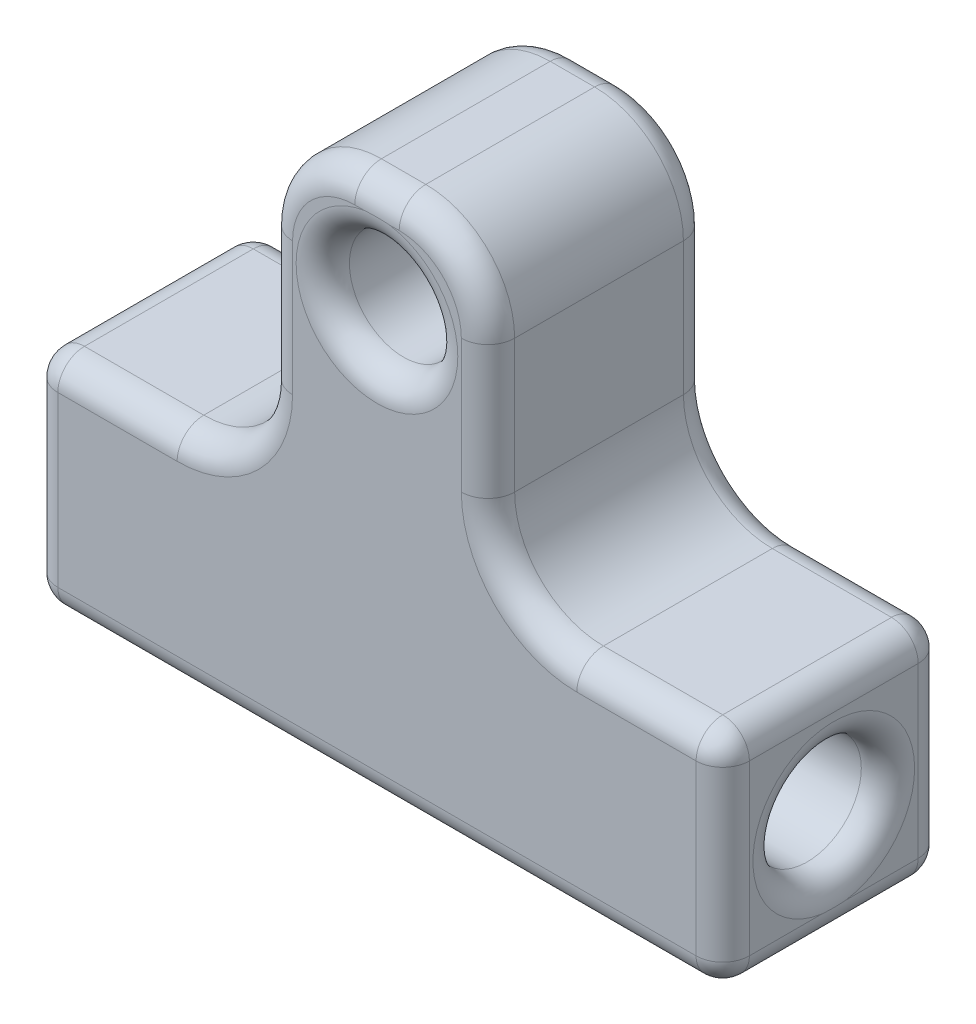
SolidWorks part; units mm, degrees
ref_plane "Front Plane" through (0, 0, 0) normal (0, 0, 1) x (1, 0, 0)
ref_plane "Top Plane" through (0, 0, 0) normal (0, 1, 0) x (1, 0, 0)
ref_plane "Right Plane" through (0, 0, 0) normal (1, 0, 0) x (0, 0, -1)
sketch "Sketch1" plane through (0, 0, 0) normal (0, 0, 1) x (1, 0, 0)
  line L0 (0, 42.6446) -> (0, -51.4876) construction
  line L1 (-40.9091, 0) -> (51.7355, 0) construction
  line L2 (22.5, -5) -> (38.9256, -5)
  line L3 (-2.5, 30) -> (2.5, 30)
  line L4 (-12.5, 20) -> (-12.5, 5)
  line L5 (-12.5, -30) -> (12.5, -30)
  line L6 (12.5, 20) -> (12.5, 5)
  line L7 (-12.5, 30) -> (12.5, -30) construction
  line L8 (-12.5, -30) -> (12.5, 30) construction
  line L9 (-38.9256, -5) -> (-22.5, -5)
  line L10 (-38.9256, -5) -> (-38.9256, -30)
  line L11 (-38.9256, -30) -> (38.9256, -30)
  line L12 (38.9256, -5) -> (38.9256, -30)
  line L13 (-38.9256, -5) -> (38.9256, -30) construction
  line L14 (-38.9256, -30) -> (38.9256, -5) construction
  arc A0 (2.5, 30) -> (12.5, 20) centre (2.5, 20) cw
  arc A1 (-2.5, 30) -> (-12.5, 20) centre (-2.5, 20) ccw
  arc A2 (12.5, 5) -> (22.5, -5) centre (22.5, 5) ccw
  arc A3 (-12.5, 5) -> (-22.5, -5) centre (-22.5, 5) cw
  circle A4 centre (0, 18) radius 6.1
  point P5 (0, 0)
  point P10 (0, -17.5)
  point P25 (12.5, -5)
  dimension "D4" = 10
  dimension "D5" = 12.2
  dimension "D1" = 25
  dimension "D2" = 60
  dimension "D3" = 25
  dimension "D6" = 12
extrude "Boss-Extrude1" add sketch "Sketch1" along normal blind 25 contours A3 L9 L10 L11 L12 L2 A2 L6 A0 L3 A1 L4 | A4
sketch "Sketch2" plane through (38.9256, 0, 0) normal (1, 0, 0) x (0, 0, -1)
  line L0 (-12.5, -5) -> (-12.5, -30) construction
  line L1 (-25, -5) -> (0, -5) construction
  line L2 (-25, -30) -> (0, -30) construction
  circle A0 centre (-12.5, -18) radius 6.1
  dimension "D1" = 12.2
  dimension "D2" = 12
extrude "Cut-Extrude1" cut sketch "Sketch2" against normal through all
fillet "Fillet1" radius 3 32 edges at (-38.9256, -5, 12.5) (-38.9256, -30, 12.5) (-38.9256, -18, 6.4) (6.1, 18, 0) (-15.4289, -2.0711, 0) (-30.7128, -5, 0) (-38.9256, -17.5, 0) (0, -30, 0) (15.4289, -2.0711, 0) (12.5, 12.5, 0) (9.5711, 27.0711, 0) (0, 30, 0) (-9.5711, 27.0711, 0) (-12.5, 12.5, 0) (30.7128, -5, 0) (6.1, 18, 25) (-9.5711, 27.0711, 25) (0, 30, 25) (9.5711, 27.0711, 25) (12.5, 12.5, 25) (15.4289, -2.0711, 25) (30.7128, -5, 25) (0, -30, 25) (-38.9256, -17.5, 25) (-30.7128, -5, 25) (-15.4289, -2.0711, 25) (-12.5, 12.5, 25) (38.9256, -30, 12.5) (38.9256, -17.5, 25) (38.9256, -5, 12.5) (38.9256, -17.5, 0) (38.9256, -18, 6.4)
